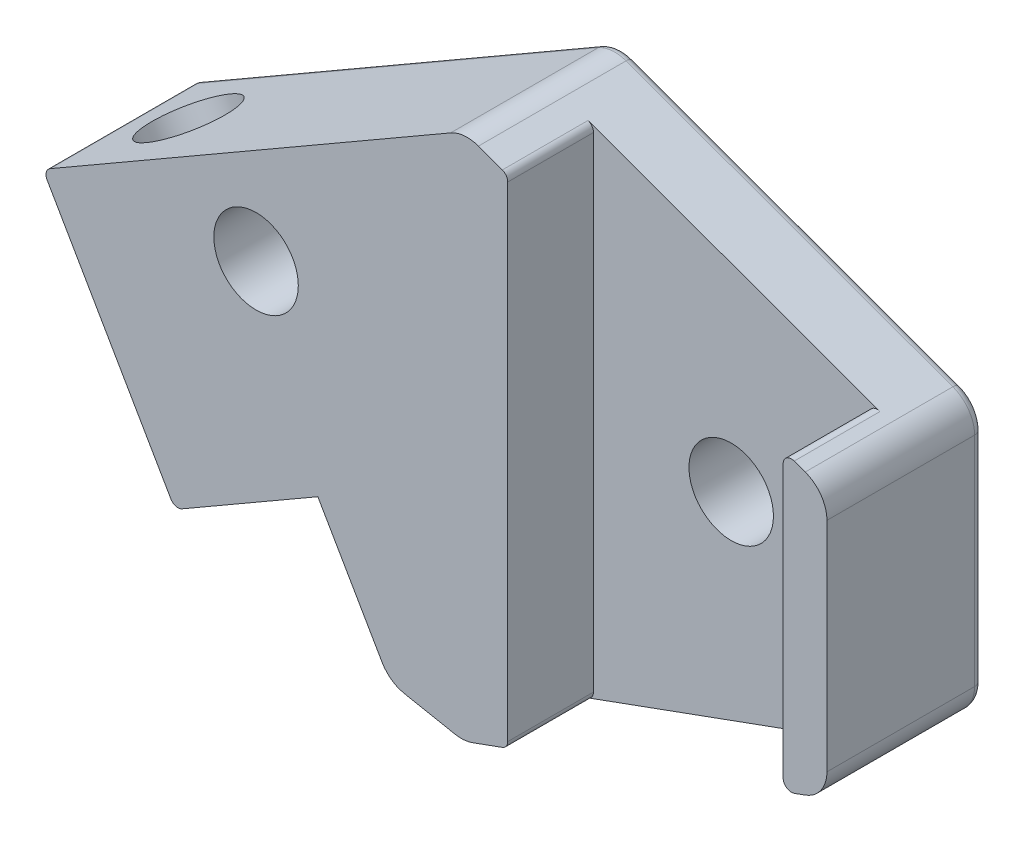
SolidWorks part; units mm, degrees
ref_plane "Front Plane" through (0, 0, 0) normal (0, 0, 1) x (1, 0, 0)
ref_plane "Top Plane" through (0, 0, 0) normal (0, 1, 0) x (1, 0, 0)
ref_plane "Right Plane" through (0, 0, 0) normal (1, 0, 0) x (0, 0, -1)
sketch "Sketch1" plane through (0, 0, 0) normal (0, 0, 1) x (1, 0, 0)
  line L0 (-11.6417, 0) -> (-2.9104, 0) construction
  line L1 (5.8208, -6.35) -> (-11.6417, -12.7)
  line L2 (5.8208, -6.35) -> (5.8208, 6.35)
  line L3 (5.8208, 6.35) -> (-11.6417, 12.7)
  line L4 (-11.6417, -12.7) -> (-11.6417, 12.7)
  line L5 (5.8208, -6.35) -> (-11.6417, 12.7) construction
  line L6 (5.8208, 6.35) -> (-11.6417, -12.7) construction
  line L7 (-2.9104, 0) -> (5.8208, 0) construction
  circle A0 centre (-2.9104, 0) radius 2.032
  point P0 (0, 0)
  dimension "D2" = 4.064
  dimension "D1" = 17.4625
  dimension "D3" = 12.7
  dimension "D4" = 25.4
extrude "Boss-Extrude1" add sketch "Sketch1" along normal blind 3.375
sketch "Sketch2" plane through (0, 0, 3.375) normal (0, 0, 1) x (1, 0, 0)
  line L0 (-11.6417, -12.7) -> (5.8208, -6.35) construction
  line L2 (-11.6417, 12.7) -> (-11.6417, -12.7)
  line L4 (-9.5354, 11.9341) -> (-9.5354, -11.9341)
  line L5 (5.8208, 6.35) -> (-11.6417, 12.7) construction
  line L7 (5.8208, 6.35) -> (5.8208, -6.35)
  line L9 (3.7146, 7.1159) -> (3.7146, -7.1159)
  line L10 (-11.6417, -12.7) -> (-9.5354, -11.9341)
  line L11 (5.8208, 6.35) -> (3.7146, 7.1159)
  line L12 (3.7146, -7.1159) -> (5.8208, -6.35)
  line L13 (-9.5354, 11.9341) -> (-11.6417, 12.7)
  circle A0 centre (-2.9104, 0) radius 6.625 construction
  dimension "D2" = 13.25
extrude "Boss-Extrude2" add sketch "Sketch2" along normal blind 4.125
sketch "Sketch4" plane through (0, 0, 0) normal (0, 0, -1) x (-1, 0, 0)
  line L0 (11.6417, 12.7) -> (31.8943, 1.0071)
  line L2 (25.5443, -9.9914) -> (11.6417, -12.7)
  line L3 (11.6417, -12.7) -> (11.6417, 12.7)
  line L4 (31.8943, 1.0071) -> (25.5443, -9.9914)
  circle A0 centre (21.6429, 2.3012) radius 2.032
  circle A1 centre (2.9104, 0) radius 2.032 construction
  dimension "D1" = 18.7325
  dimension "D2" = 2.3012
  dimension "D3" = 30
  dimension "D4" = 9.525
  dimension "D5" = 12.7
extrude "Boss-Extrude3" add sketch "Sketch4" against normal up to surface (7.5 mm away) up to face at (-10.5885, 0, 7.5)
sketch "Sketch5" plane through (-8.4097, 14.566, 0) normal (-0.5, 0.866, 0) x (0.866, 0.5, 0)
  line L0 (-27.1177, -3.75) -> (-23.3677, -3.75) construction
  line L1 (-27.1177, -7.5) -> (-27.1177, 0) construction
  line L2 (-23.3677, -3.75) -> (-23.3677, 0) construction
  line L3 (-27.1177, 0) -> (-3.732, 0) construction
  circle A0 centre (-23.3677, -3.75) radius 2.032
  dimension "D1" = 4.064
extrude "Cut-Extrude1" cut sketch "Sketch5" against normal through all
ref_plane "Plane1" through (-2.0597, 3.5675, 0) normal (-0.5, 0.866, 0) x (0.866, 0.5, 0)
sketch "Sketch6" plane through (-2.0597, 3.5675, 0) normal (-0.5, 0.866, 0) x (0.866, 0.5, 0)
  line L0 (-19.1802, -7.5) -> (-19.1802, 0)
  line L1 (-27.1177, -7.5) -> (-3.732, -7.5) construction
  line L2 (-27.1177, 0) -> (-3.732, 0) construction
  line L3 (-19.1802, 0) -> (-27.1177, 0)
  line L4 (-27.1177, 0) -> (-27.1177, -7.5)
  line L5 (-27.1177, -7.5) -> (-19.1802, -7.5)
  dimension "D1" = 7.9375
extrude "Cut-Extrude2" cut sketch "Sketch6" against normal through all
fillet "Fillet1" radius 1.5875 5 edges at (5.8208, -6.35, 3.75) (5.8208, 6.35, 3.75) (-11.6417, 12.7, 3.75) (-15.2172, -12.0034, 3.75) (-11.6417, -12.7, 3.75)
fillet "Fillet2" radius 0.3969 19 edges at (3.7146, -7.1159, 5.4375) (3.7146, 7.1159, 5.4375) (5.5336, 6.1488, 0) (5.8208, 0, 0) (5.5336, -6.1488, 0) (-3.226, -9.6398, 0) (-3.0852, 9.5886, 0) (-17.1245, -8.6999, 0) (-15.1261, -11.8757, 0) (-13.2907, -12.3787, 0) (-11.6463, -12.6402, 0) (-22.0884, 6.6686, 0) (-11.6273, 12.5366, 0) (-22.1073, -8.007, 0) (-28.7193, -4.4921, 0) (-31.8943, 1.0071, 3.75) (-25.5443, -9.9914, 3.75) (-9.5354, -11.9341, 5.4375) (-9.5354, 11.9341, 5.4375)
